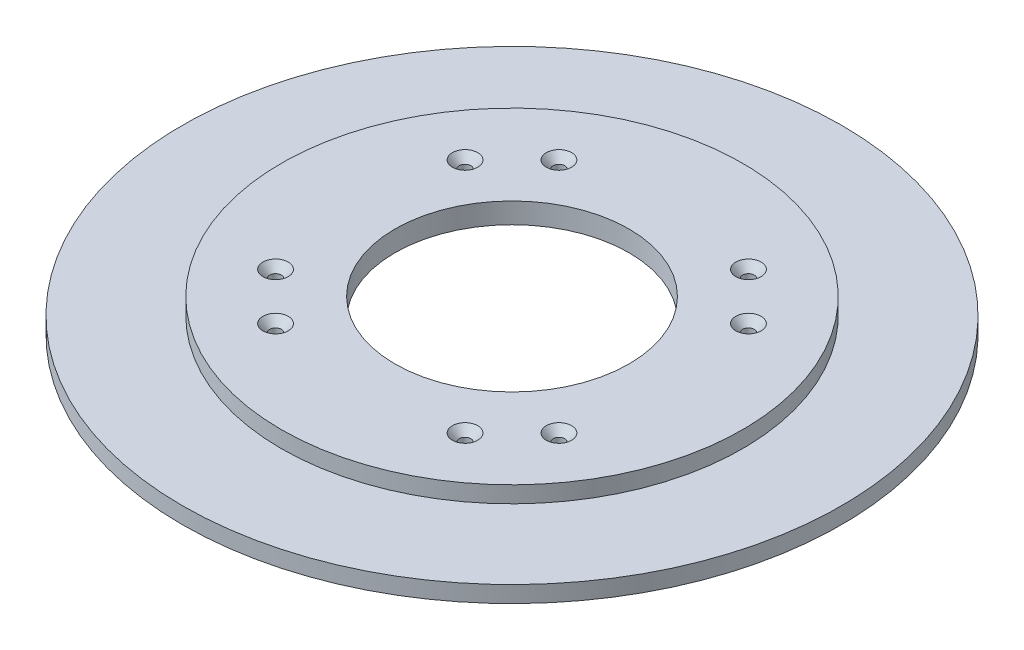
SolidWorks part; units mm, degrees
material "6061-T6 (SS)"
ref_plane "Front Plane" through (0, 0, 0) normal (0, 0, 1) x (1, 0, 0)
ref_plane "Top Plane" through (0, 0, 0) normal (0, 1, 0) x (1, 0, 0)
ref_plane "Right Plane" through (0, 0, 0) normal (1, 0, 0) x (0, 0, -1)
sketch "Sketch1" plane through (0, 0, 0) normal (0, 1, 0) x (1, 0, 0)
  line L5 (-85.725, -85.725) -> (85.725, 85.725) construction
  line L6 (-85.725, 85.725) -> (85.725, -85.725) construction
  circle A0 centre (0, 0) radius 54.61 construction
  circle A1 centre (0, 0) radius 127
  point P0 (0, 0)
  point P16 (-67.31, 0)
  point P18 (0, 76.2)
  dimension "D4" = 109.22
  dimension "D7" = 254
  dimension "D1" = 171.45
  dimension "D2" = 171.45
extrude "Boss-Extrude1" add sketch "Sketch1" along normal blind 12.7
hole_wizard "CSK for #8 Flat Head Machine Screw1" positions "Sketch3" profile "Sketch2" countersink size "#8" standard "ANSI Inch" end condition through all
sketch "Sketch3" plane through (0, 12.7, 0) normal (0, 1, 0) x (-1, 0, 0)
  line L0 (-36.5125, -54.61) -> (0, 0) construction
  line L1 (0, 0) -> (36.5125, -54.61) construction
  line L2 (36.5125, -54.61) -> (-36.5125, -54.61) construction
  line L5 (-54.61, -36.5125) -> (-54.61, 36.5125) construction
  line L8 (0, 0) -> (-54.61, -36.5125) construction
  line L11 (0, 0) -> (-54.61, 36.5125) construction
  line L14 (0, 0) -> (-36.5125, 54.61) construction
  line L15 (-36.5125, 54.61) -> (36.5125, 54.61) construction
  line L16 (36.5125, 54.61) -> (0, 0) construction
  line L17 (0, 0) -> (54.61, 36.5125) construction
  line L18 (54.61, 36.5125) -> (54.61, -36.5125) construction
  line L19 (54.61, -36.5125) -> (0, 0) construction
  point P0 (36.5125, -54.61)
  point P1 (-36.5125, -54.61)
  point P19 (36.5125, 54.61)
  point P21 (-36.5125, 54.61)
  point P23 (-54.61, -36.5125)
  point P25 (-54.61, 36.5125)
  point P27 (54.61, 36.5125)
  point P29 (54.61, -36.5125)
  dimension "D1" = 73.025
  dimension "D3" = 109.22
sketch "Sketch2" plane through (-36.5125, 12.7, -54.61) normal (1, 0, 0) x (0, 0, 1)
  line L0 (0, 0) -> (0, 12.7)
  line L1 (0, 12.7) -> (2.2479, 12.7)
  line L2 (2.2479, 12.7) -> (2.2479, 3.0265)
  line L3 (2.2479, 3.0265) -> (4.8788, 0)
  line L5 (4.8788, 0) -> (0, 0)
  line L6 (-2.2479, 3.0265) -> (-4.8788, 0) construction
  line L11 (0, -6.35) -> (0, 107.95) construction
  dimension "Thru Hole Dia." = 4.4958
  dimension "Thru Hole Depth" = 12.7
  dimension "Near C'Sink Dia." = 9.7576
  dimension "Near C'Sink Angle" = 82
ref_axis "Axis1" through (0, 0, 0) along (0, 1, 0)
pattern_circular "CirPattern1" count 2 over 360 about axis through (0, 0, 0) along (0, 1, 0) of "CSK for #8 Flat Head Machine Screw1"
sketch "Sketch4" plane through (0, 12.7, 0) normal (0, 1, 0) x (1, 0, 0)
  circle A0 centre (0, 0) radius 45.085
  dimension "D1" = 90.17
extrude "Cut-Extrude1" cut sketch "Sketch4" against normal through all
sketch "Sketch6" plane through (0, 12.7, 0) normal (0, 1, 0) x (1, 0, 0)
  circle A0 centre (0, 0) radius 88.9
  circle A1 centre (0, 0) radius 127 construction
  circle A2 centre (0, 0) radius 127
  dimension "D1" = 177.8
extrude "Cut-Extrude3" cut sketch "Sketch6" against normal blind 6.35
sketch "Sketch5" plane through (0, 0, 0) normal (0, 1, 0) x (1, 0, 0)
  line L0 (0, 134.7756) -> (0, 0) construction
  line L1 (0, 0) -> (-157.1627, 0) construction
  line L2 (-82.55, 0) -> (-60.96, 0)
  line L3 (-60.96, 0) -> (-60.96, 39.1428)
  line L4 (-60.96, 39.1428) -> (-39.1428, 60.96) construction
  line L5 (-39.1428, 60.96) -> (0, 60.96)
  line L6 (0, 60.96) -> (0, 82.55)
  line L7 (-60.96, 39.1428) -> (-54.61, 36.5125) construction
  line L8 (-36.5125, 54.61) -> (-39.1428, 60.96) construction
  line L9 (-54.61, 36.5125) -> (-54.61, -36.5125) construction
  arc A0 (0, 82.55) -> (-44.6026, 69.463) centre (0, 0) ccw
  circle A1 centre (0, 0) radius 88.9 construction
  arc A2 (-60.96, 39.1428) -> (-69.463, 44.6026) centre (-65.2115, 41.8727) ccw
  arc A3 (-69.463, 44.6026) -> (-82.55, 0) centre (0, 0) ccw
  arc A4 (-44.6026, 69.463) -> (-39.1428, 60.96) centre (-41.8727, 65.2115) ccw
  circle A5 centre (0, 0) radius 72.445 construction
  dimension "D1" = 6.35
  dimension "D2" = 6.35
  dimension "D6" = 39.1428
  dimension "D7" = 36.5125
  dimension "D5" = 39.1428
  dimension "D4" = 5.0525
  dimension "D9" = 5.0525
  dimension "D3" = 6.35
  dimension "D8" = 36.5125
extrude "Cut-Extrude2" cut sketch "Sketch5" along normal offset from surface (11.1125 mm away) 1.5875 up to face at (-54.61, 12.7, -31.6337)
sketch "Sketch7" plane through (0, 0, 0) normal (0, -1, 0) x (1, 0, 0)
  line L0 (0, 0) -> (-120.65, 0)
  line L1 (0, 0) -> (0, -120.65)
  arc A0 (-120.65, 0) -> (0, -120.65) centre (0, 0) ccw
  circle A1 centre (0, 0) radius 127 construction
  dimension "D1" = 6.35
extrude "Cut-Extrude4" cut sketch "Sketch7" against normal offset from surface (4.7625 mm away) 1.5875 up to face at (0, 6.35, 88.9)
pattern_circular "CirPattern2" count 4 over 360 about axis through (0, 0, 0) along (0, 1, 0) of "Cut-Extrude4", "Cut-Extrude2"
